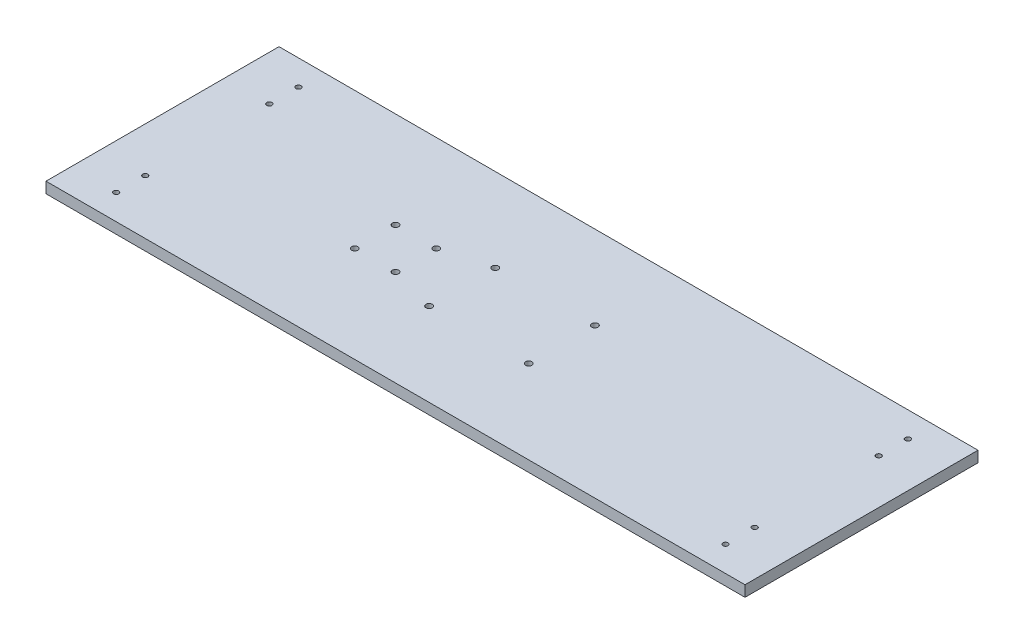
SolidWorks part; units mm, degrees
ref_plane "Front Plane" through (0, 0, 0) normal (0, 0, 1) x (1, 0, 0)
ref_plane "Top Plane" through (0, 0, 0) normal (0, 1, 0) x (1, 0, 0)
ref_plane "Right Plane" through (0, 0, 0) normal (1, 0, 0) x (0, 0, -1)
sketch "Sketch1" plane through (0, 0, 0) normal (0, 1, 0) x (1, 0, 0)
  line L1 (0, 0) -> (609.6, 0)
  line L2 (0, 0) -> (0, 203.2)
  line L3 (0, 203.2) -> (609.6, 203.2)
  line L4 (609.6, 0) -> (609.6, 203.2)
  line L5 (304.8, 203.2) -> (304.8, 0) construction
  line L6 (0, 101.6) -> (609.6, 101.6) construction
  point P124 (304.8, 101.6)
  dimension "D1" = 609.6
  dimension "D2" = 203.2
extrude "Table Blank" add sketch "Sketch1" along normal blind 9.525
sketch "Table Location" plane through (0, 9.525, 0) normal (0, 1, 0) x (1, 0, 0)
  line L0 (0, 101.6) -> (609.6, 101.6) construction
  line L1 (228.6, 152.4) -> (381, 152.4) construction
  line L2 (228.6, 152.4) -> (228.6, 50.8) construction
  line L3 (228.6, 50.8) -> (381, 50.8) construction
  line L4 (381, 152.4) -> (381, 50.8) construction
  line L5 (304.8, 50.8) -> (304.8, 152.4) construction
  line L6 (228.6, 101.6) -> (381, 101.6) construction
  line L7 (304.8, 203.2) -> (304.8, 0) construction
  line L9 (261.366, 130.429) -> (348.234, 130.429) construction
  line L10 (261.366, 130.429) -> (261.366, 72.771) construction
  line L11 (261.366, 72.771) -> (348.234, 72.771) construction
  line L12 (348.234, 130.429) -> (348.234, 72.771) construction
  line L13 (304.8, 72.771) -> (304.8, 130.429) construction
  line L14 (261.366, 101.6) -> (348.234, 101.6) construction
  circle A0 centre (261.366, 72.771) radius 2.5 construction
  circle A1 centre (261.366, 130.429) radius 2.5 construction
  circle A2 centre (348.234, 130.429) radius 2.5 construction
  circle A3 centre (348.234, 72.771) radius 2.5 construction
  point P124 (304.8, 101.6)
  point P224 (304.8, 101.6)
  dimension "D1" = 152.4
  dimension "D2" = 101.6
  dimension "D3" = 86.868
  dimension "D4" = 57.658
hole_wizard "Table Holes (M5 Clearance)" positions "Sketch4" profile "Sketch5" hole size "M5" standard "ANSI Metric" end condition through all
sketch "Sketch4" plane through (0, 9.525, 0) normal (0, 1, 0) x (1, 0, 0)
  point P0 (261.366, 130.429)
  point P3 (348.234, 130.429)
  point P6 (348.234, 72.771)
  point P9 (261.366, 72.771)
sketch "Sketch5" plane through (261.366, 9.525, -130.429) normal (1, 0, 0) x (0, 0, 1)
  line L0 (0, 0) -> (0, 9.525)
  line L1 (0, 9.525) -> (2.75, 9.525)
  line L2 (2.75, 9.525) -> (2.75, 0)
  line L5 (2.75, 0) -> (0, 0)
  line L11 (0, -6.35) -> (0, 107.95) construction
  dimension "Thru Hole Dia." = 5.5
  dimension "Thru Hole Depth" = 9.525
sketch "Runner Location" plane through (0, 9.525, 0) normal (0, 1, 0) x (1, 0, 0)
  line L0 (0, 101.6) -> (609.6, 101.6) construction
  line L1 (177.8, 127) -> (228.6, 127) construction
  line L2 (177.8, 127) -> (177.8, 76.2) construction
  line L3 (177.8, 76.2) -> (228.6, 76.2) construction
  line L4 (228.6, 127) -> (228.6, 76.2) construction
  line L5 (203.2, 76.2) -> (203.2, 127) construction
  line L6 (177.8, 101.6) -> (228.6, 101.6) construction
  line L7 (228.6, 152.4) -> (228.6, 50.8) construction
  line L8 (185.42, 119.38) -> (185.42, 83.82) construction
  line L9 (185.42, 83.82) -> (220.98, 83.82) construction
  line L10 (220.98, 119.38) -> (220.98, 83.82) construction
  line L11 (185.42, 119.38) -> (220.98, 119.38) construction
  point P136 (203.2, 101.6)
  dimension "D1" = 50.8
  dimension "D2" = 7.62
hole_wizard "Runner Holes" positions "Sketch7" profile "Sketch8" hole size "M5" standard "ANSI Metric" end condition through all
sketch "Sketch7" plane through (0, 9.525, 0) normal (0, 1, 0) x (1, 0, 0)
  point P0 (185.42, 119.38)
  point P3 (220.98, 119.38)
  point P6 (220.98, 83.82)
  point P9 (185.42, 83.82)
sketch "Sketch8" plane through (185.42, 9.525, -119.38) normal (1, 0, 0) x (0, 0, 1)
  line L0 (0, 0) -> (0, 9.525)
  line L1 (0, 9.525) -> (2.75, 9.525)
  line L2 (2.75, 9.525) -> (2.75, 0)
  line L5 (2.75, 0) -> (0, 0)
  line L11 (0, -6.35) -> (0, 107.95) construction
  dimension "Thru Hole Dia." = 5.5
  dimension "Thru Hole Depth" = 9.525
sketch "Wheel Location" plane through (0, 9.525, 0) normal (0, 1, 0) x (1, 0, 0)
  line L0 (55.88, 187.452) -> (55.88, 15.748) construction
  line L1 (0, 101.6) -> (609.6, 101.6) construction
  line L2 (0, 0) -> (0, 203.2) construction
  line L3 (30.1879, 187.452) -> (45.4279, 187.452) construction
  line L4 (25.6921, 187.452) -> (30.1879, 187.452) construction
  line L5 (25.6921, 187.452) -> (25.6921, 15.748) construction
  line L6 (25.6921, 15.748) -> (30.1879, 15.748) construction
  line L7 (30.1879, 187.452) -> (30.1879, 15.748) construction
  line L8 (27.94, 15.748) -> (27.94, 187.452) construction
  line L9 (25.6921, 101.6) -> (30.1879, 101.6) construction
  line L10 (30.1879, 15.748) -> (45.4279, 15.748) construction
  line L11 (30.1879, 15.748) -> (30.1879, 53.848) construction
  line L12 (30.1879, 53.848) -> (45.4279, 53.848) construction
  line L13 (45.4279, 15.748) -> (45.4279, 53.848) construction
  line L14 (45.4279, 187.452) -> (45.4279, 149.352) construction
  line L15 (30.1879, 149.352) -> (45.4279, 149.352) construction
  point P2 (55.88, 101.6)
  point P11 (39.0779, 22.098)
  point P15 (0, 0)
  point P16 (39.0779, 47.498)
  point P17 (39.0779, 181.102)
  point P18 (39.0779, 155.702)
  point P487 (27.94, 101.6)
  dimension "D1" = 171.704
  dimension "D2" = 55.88
  dimension "D3" = 4.4958
  dimension "D4" = 27.94
  dimension "D5" = 6.35
  dimension "D7" = 15.24
  dimension "D8" = 38.1
  dimension "D6" = 6.35
  dimension "D9" = 25.4
hole_wizard "Wheel Holes (M4 Clearance)" positions "Sketch10" profile "Sketch11" hole size "M4" standard "ANSI Metric" end condition through all
sketch "Sketch10" plane through (0, 9.525, 0) normal (0, 1, 0) x (1, 0, 0)
  point P0 (39.0779, 181.102)
  point P3 (39.0779, 155.702)
  point P6 (39.0779, 47.498)
  point P9 (39.0779, 22.098)
sketch "Sketch11" plane through (39.0779, 9.525, -181.102) normal (1, 0, 0) x (0, 0, 1)
  line L0 (0, 0) -> (0, 9.525)
  line L1 (0, 9.525) -> (2.25, 9.525)
  line L2 (2.25, 9.525) -> (2.25, 0)
  line L5 (2.25, 0) -> (0, 0)
  line L11 (0, -6.35) -> (0, 107.95) construction
  dimension "Thru Hole Dia." = 4.5
  dimension "Thru Hole Depth" = 9.525
ref_plane "Plane1" through (304.8, 0, 0) normal (-1, 0, 0) x (0, 0, 1)
mirror "Mirror1" about plane through (304.8, 0, 0) normal (-1, 0, 0) of "Wheel Holes (M4 Clearance)"
equation "\"baseplate x\"= 24"
equation "\"baseplate y\"= 8"
equation "\"D1@Sketch1\"=\"baseplate x\""
equation "\"D2@Sketch1\"=\"baseplate y\""
equation "\"stock thick\"= 3 / 8"
equation "\"D1@Table Blank\" = \"stock thick\""
equation "\"table x\"= 6"
equation "\"table y\"= 4"
equation "\"D1@Table Location\" = \"table x\""
equation "\"D2@Table Location\" = \"table y\""
equation "\"width wheelmount\"= 6.76"
equation "\"offset wheelmount\"= 2.2"
equation "\"D2@Wheel Location\" = \"offset wheelmount\""
equation "\"D1@Wheel Location\" = \"width wheelmount\""
equation "\"D4@Wheel Location\" = \"D2@Wheel Location\" / 2"
